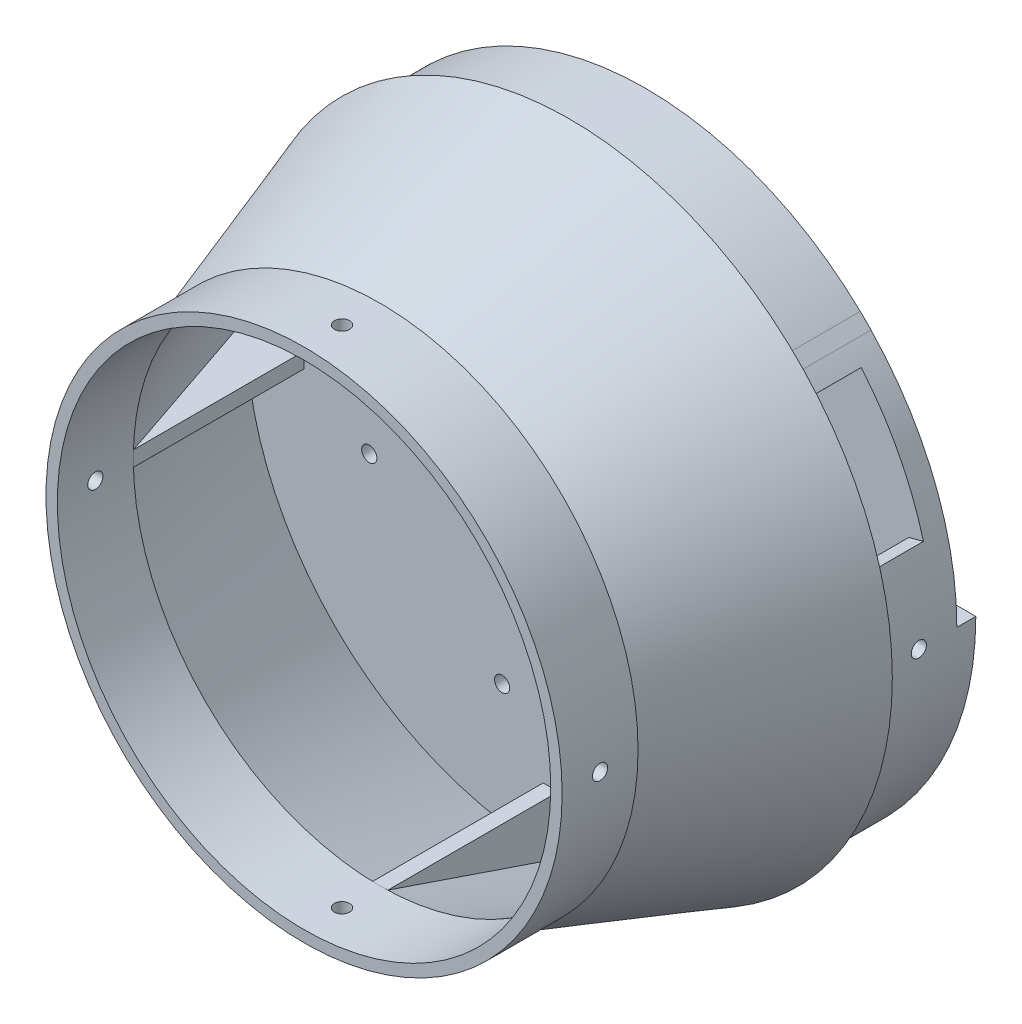
SolidWorks part; units mm, degrees
ref_plane "Front Plane" through (0, 0, 0) normal (0, 0, 1) x (1, 0, 0)
ref_plane "Top Plane" through (0, 0, 0) normal (0, 1, 0) x (1, 0, 0)
ref_plane "Right Plane" through (0, 0, 0) normal (1, 0, 0) x (0, 0, -1)
sketch "Sketch10" plane through (0, 0, 0) normal (0, 1, 0) x (1, 0, 0)
  line L9 (68, 0) -> (85, 50)
  line L10 (65, 0) -> (65, -20)
  line L11 (65, -20) -> (68, -20)
  line L12 (68, -20) -> (68, 0)
  line L13 (85, 50) -> (0, 50)
  line L14 (0, 50) -> (0, 45)
  line L16 (0, 0) -> (0, 90.5218) construction
  line L17 (65, 0) -> (80.3, 45)
  line L18 (0, 45) -> (80.3, 45)
  dimension "D1" = 65
  dimension "D2" = 20
  dimension "D3" = 50
  dimension "D4" = 85
  dimension "D5" = 68
  dimension "D6" = 5
revolve "Revolve2" add sketch "Sketch10" angle 360 about L16
sketch "Sketch12" plane through (0, 0, 0) normal (0, 1, 0) x (1, 0, 0)
  line L4 (-80.3, 45) -> (-65, 0)
  line L5 (-65, 0) -> (-65, 45)
  line L6 (-80.3, 45) -> (80.3, 45) construction
  line L7 (-65, 45) -> (-80.3, 45)
extrude "Boss-Extrude5" add sketch "Sketch12" along normal blind 2 and the other way blind 2
pattern_circular "CirPattern3" count 4 every 90 about axis through (0, 0, -50) along (0, 0, 1) of "Boss-Extrude5"
sketch "Sketch13" plane through (0, 0, -50) normal (0, 0, -1) x (-1, 0, 0)
  arc A0 (70, 42.7083) -> (70, -42.7083) centre (0, 0) ccw
  arc A1 (70, 34.4093) -> (70, -34.4093) centre (0, 0) ccw
  circle A2 centre (0, 0) radius 82 construction
  circle A3 centre (0, 0) radius 78 construction
  circle A4 centre (0, 0) radius 82
  circle A5 centre (0, 0) radius 78
  dimension "D1" = 164
  dimension "D2" = 4
extrude "Boss-Extrude6" add sketch "Sketch13" along normal blind 20 contours A0 A4 A5 A1 region at (-76.7102, 21.5537, -50)
sketch "Sketch14" plane through (0, 0, 0) normal (0, 1, 0) x (1, 0, 0)
  line L0 (-65, -20) -> (65, -20) construction
  circle A0 centre (0, -10) radius 2
  dimension "D1" = 4
  dimension "D2" = 10
extrude "Cut-Extrude1" cut sketch "Sketch14" against normal blind 95
pattern_circular "CirPattern4" count 4 every 90 about axis through (0, 0, 20) along (0, 0, 1) of "Cut-Extrude1"
sketch "Sketch16" plane through (0, 0, 0) normal (0, 1, 0) x (1, 0, 0)
  line L0 (85, 50) -> (-85, 50) construction
  circle A0 centre (0, 60) radius 2
  dimension "D1" = 4
  dimension "D2" = 10
extrude "Cut-Extrude2" cut sketch "Sketch16" against normal blind 94
pattern_circular "CirPattern5" count 2 every 90 about axis through (0, 0, -70) along (0, 0, -1) of "Cut-Extrude2" other way count 2
sketch "Sketch17" plane through (0, 0, -50) normal (0, 0, -1) x (-1, 0, 0)
  line L0 (0, 0) -> (-47.8133, 12.8115) construction
  line L1 (0, 0) -> (-12.8115, 47.8133) construction
  circle A0 centre (-47.8133, 12.8115) radius 2
  circle A4 centre (-12.8115, 47.8133) radius 2
  circle A5 centre (12.8115, -47.8133) radius 2
  circle A6 centre (47.8133, -12.8115) radius 2
  point P12 (0, 0)
  point P16 (0, 0)
  dimension "D1" = 4
  dimension "D2" = 49.5
  dimension "D4" = 60
  dimension "D3" = 2
  dimension "D5" = 2
extrude "Cut-Extrude4" cut sketch "Sketch17" against normal blind 900
sketch "Sketch19" plane through (0, 0, -70) normal (0, 0, -1) x (-1, 0, 0)
  line L0 (0, 0) -> (0, 85) construction
  line L1 (0, 0) -> (-79.2059, 21.2232)
  line L6 (0, 0) -> (-62.8156, 52.7086)
  circle A0 centre (0, 0) radius 85 construction
  arc A2 (-62.8156, 52.7086) -> (-79.2059, 21.2232) centre (0, 0) ccw
  dimension "D1" = 75
  dimension "D2" = 50
extrude "Cut-Extrude7" cut sketch "Sketch19" against normal blind 20
mirror "Mirror1" about plane through (0, 0, 0) normal (1, 0, 0) of "Cut-Extrude7"
sketch "Sketch22" plane through (0, 0, -70) normal (0, 0, -1) x (-1, 0, 0)
  circle A2 centre (0, 0) radius 82
  circle A3 centre (0, 0) radius 60
  arc M2 (-59.7515, 50.1374) -> (59.7515, 50.1374) centre (0, 0) cw
  line M3 (59.7515, 50.1374) -> (62.8156, 52.7086)
  arc M4 (62.8156, 52.7086) -> (-62.8156, 52.7086) centre (0, 0) ccw
  line M5 (-62.8156, 52.7086) -> (-59.7515, 50.1374)
  dimension "D1" = 120
extrude "Boss-Extrude8" add sketch "Sketch22" against normal blind 6 contours A2 A3 M5 M3 M2 | M5 M2 M3 M4 region at (27.262, -74.9018, -70) region at (-60.4504, 52.4159, -70)
sketch "Sketch24" plane through (0, 0, -50) normal (0, 0, -1) x (-1, 0, 0)
  circle A0 centre (0, 0) radius 25
  dimension "D1" = 50
extrude "Cut-Extrude8" cut sketch "Sketch24" against normal blind 5
ref_plane "Plane1" through (0, 0, 0) normal (-0.7071, 0.7071, 0) x (0.7071, 0.7071, 0)
sketch "Sketch28" plane through (0, 0, 0) normal (-0.7071, 0.7071, 0) x (0.7071, 0.7071, 0)
  line L0 (-68, 50) -> (-68, 70)
  line L1 (82, 70) -> (-82, 70) construction
  line L2 (-68, 70) -> (-82, 70)
  line L3 (-82, 70) -> (-82, 50)
  line L4 (85, 50) -> (-85, 50) construction
  line L5 (-82, 70) -> (-82, 50) construction
  line L6 (-82, 50) -> (-68, 50)
extrude "Boss-Extrude9" add sketch "Sketch28" along normal blind 2 and the other way blind 2
pattern_circular "CirPattern6" count 4 every 90 about axis through (0, 0, -70) along (0, 0, -1) of "Boss-Extrude9"
sketch "Sketch29" plane through (0, 0, -70) normal (0, 0, -1) x (-1, 0, 0)
  line L6 (-75, 0) -> (-82, 0)
  line L8 (75, 0) -> (82, 0)
  arc A0 (-82, 0) -> (82, 0) centre (0, 0) ccw
  arc A2 (-75, 0) -> (75, 0) centre (0, 0) ccw
  dimension "D3" = 150
extrude "Boss-Extrude10" add sketch "Sketch29" along normal blind 5 contours A0 L8 A2 L6
sketch "Sketch30" plane through (0, 0, -50) normal (0, 0, -1) x (-1, 0, 0)
  line L3 (-53.6231, 44.9951) -> (-58.9854, 49.4946)
  line L5 (58.9854, 49.4946) -> (53.6231, 44.9951)
  line L6 (69.7336, 6.1009) -> (76.707, 6.711)
  line L7 (-69.4142, 9.0369) -> (-76.3556, 9.9406)
  line L10 (-69.4142, 9.0369) -> (-76.3556, 9.9406)
  line L12 (-53.6231, 44.9951) -> (-58.9854, 49.4946)
  line L13 (53.6231, 44.9951) -> (58.9854, 49.4946)
  line L14 (69.7336, 6.1009) -> (76.707, 6.711)
  arc A0 (-53.6231, 44.9951) -> (-69.4142, 9.0369) centre (0, 0) ccw
  arc A1 (69.7336, 6.1009) -> (53.6231, 44.9951) centre (0, 0) ccw
  arc A2 (-58.9854, 49.4946) -> (-76.3556, 9.9406) centre (0, 0) ccw
  arc A3 (76.707, 6.711) -> (58.9854, 49.4946) centre (0, 0) ccw
  dimension "D1" = 140
  dimension "D2" = 154
extrude "Cut-Extrude11" cut sketch "Sketch30" against normal blind 10 and the other way blind 10 contours L3 A2 L7 A0 region at (66.4437, 29.1789, -50)
extrude "Cut-Extrude12" cut sketch "Sketch30<5>" against normal blind 10 contours L6 A3 L5 A1 region at (-66.9048, 27.7129, -50)
sketch "Sketch30<5>" plane through (0, 0, -50) normal (0, 0, -1) x (-1, 0, 0) same geometry as "Sketch30"
